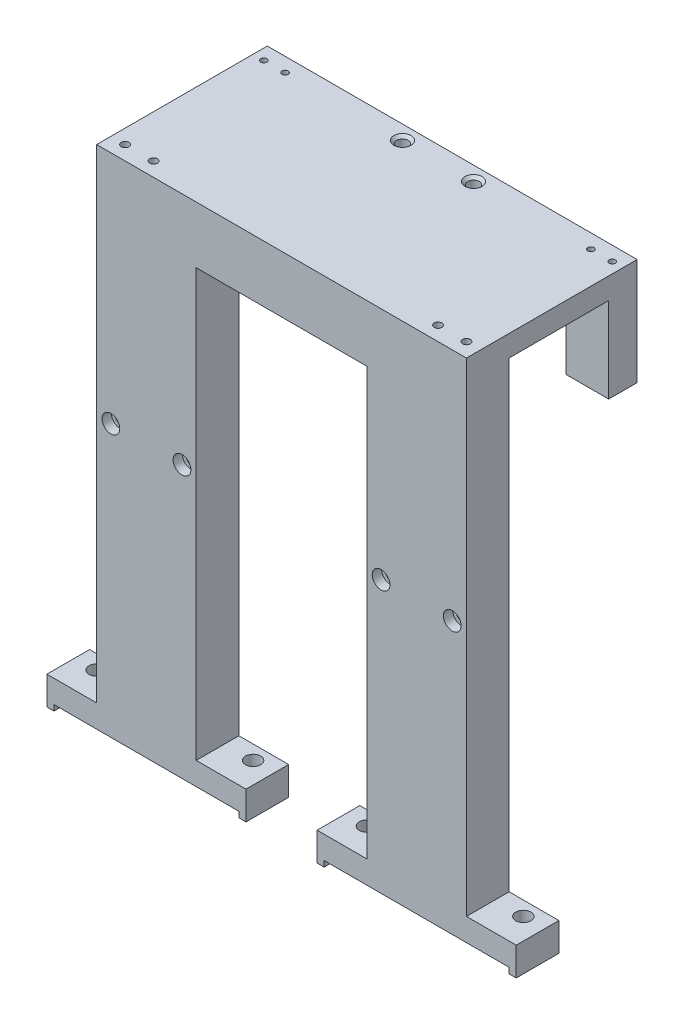
SolidWorks part; units mm, degrees
material "6061 Alloy"
ref_plane "Front Plane" through (0, 0, 0) normal (0, 0, 1) x (1, 0, 0)
ref_plane "Top Plane" through (0, 0, 0) normal (0, 1, 0) x (1, 0, 0)
ref_plane "Right Plane" through (0, 0, 0) normal (1, 0, 0) x (0, 0, -1)
sketch "Sketch1" plane through (0, 0, 0) normal (0, 0, 1) x (1, 0, 0)
  line L1 (-82.55, -114.3) -> (82.55, -114.3)
  line L2 (-82.55, -114.3) -> (-82.55, 114.3)
  line L3 (-82.55, 114.3) -> (82.55, 114.3)
  line L4 (82.55, -114.3) -> (82.55, 114.3)
  line L5 (-82.55, -114.3) -> (82.55, 114.3) construction
  line L6 (-82.55, 114.3) -> (82.55, -114.3) construction
  point P0 (0, 0)
  dimension "D1" = 228.6
  dimension "D2" = 165.1
extrude "Boss-Extrude1" add sketch "Sketch1" along normal blind 19.05
sketch "Sketch2" plane through (0, 0, 19.05) normal (0, 0, 1) x (1, 0, 0)
  line L0 (-82.55, -114.3) -> (82.55, -114.3) construction
  line L1 (-38.1, -114.3) -> (38.1, -114.3)
  line L2 (-38.1, -114.3) -> (-38.1, 88.9)
  line L3 (-38.1, 88.9) -> (38.1, 88.9)
  line L4 (38.1, -114.3) -> (38.1, 88.9)
  line L5 (-82.55, 114.3) -> (-82.55, -114.3) construction
  dimension "D1" = 203.2
  dimension "D2" = 76.2
  dimension "D3" = 44.45
extrude "Cut-Extrude1" cut sketch "Sketch2" against normal through all
sketch "Sketch3" plane through (0, 0, 0) normal (0, 0, -1) x (-1, 0, 0)
  line L0 (82.55, 114.3) -> (82.55, -114.3) construction
  line L1 (-82.55, 114.3) -> (82.55, 114.3)
  line L2 (-82.55, 114.3) -> (-82.55, 104.775)
  line L3 (-82.55, 104.775) -> (82.55, 104.775)
  line L4 (82.55, 114.3) -> (82.55, 104.775)
  dimension "D1" = 9.525
extrude "Boss-Extrude2" add sketch "Sketch3" along normal blind 57.15
sketch "Sketch4" plane through (0, 0, -57.15) normal (0, 0, -1) x (-1, 0, 0)
  line L7 (-82.55, 104.775) -> (-63.5, 104.775)
  line L8 (-82.55, 104.775) -> (-82.55, 66.675)
  line L9 (-82.55, 66.675) -> (-63.5, 66.675)
  line L10 (-63.5, 104.775) -> (-63.5, 66.675)
  dimension "D1" = 38.1
  dimension "D2" = 19.05
extrude "Boss-Extrude3" add sketch "Sketch4" against normal blind 12.7
mirror "Mirror1" about plane through (0, 0, 0) normal (1, 0, 0) of "Boss-Extrude3"
sketch "Sketch7" plane through (0, 0, 19.05) normal (0, 0, 1) x (1, 0, 0)
  line L0 (-82.55, -114.3) -> (-38.1, -114.3) construction
  line L1 (-104.775, -101.6) -> (-15.875, -101.6)
  line L2 (-104.775, -101.6) -> (-104.775, -114.3)
  line L3 (-104.775, -114.3) -> (-15.875, -114.3)
  line L4 (-15.875, -101.6) -> (-15.875, -114.3)
  line L5 (-104.775, -101.6) -> (-15.875, -114.3) construction
  line L6 (-104.775, -114.3) -> (-15.875, -101.6) construction
  line L7 (-82.55, 114.3) -> (-82.55, -114.3) construction
  point P0 (-60.325, -107.95)
  dimension "D1" = 0
  dimension "D2" = 88.9
  dimension "D3" = 22.225
  dimension "D4" = 12.7
extrude "Boss-Extrude4" add sketch "Sketch7" against normal blind 19.05
sketch "Sketch8" plane through (0, -114.3, 0) normal (0, -1, 0) x (-1, 0, 0)
  line L0 (104.775, -19.05) -> (15.875, -19.05) construction
  line L1 (101.6, 0) -> (19.05, 0)
  line L2 (101.6, 0) -> (101.6, -19.05)
  line L3 (101.6, -19.05) -> (19.05, -19.05)
  line L4 (19.05, 0) -> (19.05, -19.05)
  line L5 (101.6, 0) -> (19.05, -19.05) construction
  line L6 (101.6, -19.05) -> (19.05, 0) construction
  line L8 (104.775, 0) -> (104.775, -19.05) construction
  line L9 (15.875, 0) -> (15.875, -19.05) construction
  point P0 (60.325, -9.525)
  dimension "D1" = 19.05
  dimension "D2" = 3.175
  dimension "D3" = 3.175
extrude "Cut-Extrude4" cut sketch "Sketch8" against normal blind 2.54
mirror "Mirror3" about plane through (0, 0, 0) normal (1, 0, 0) of "Cut-Extrude4", "Boss-Extrude4"
hole_wizard "#8-32 Tapped Hole1" positions "Sketch11" profile "Sketch10" tap size "#8-32" standard "ANSI Inch"
sketch "Sketch11" plane through (0, 114.3, 0) normal (0, 1, 0) x (1, 0, 0)
  line L0 (-82.55, 0) -> (-82.55, -19.05) construction
  line L1 (-82.55, -19.05) -> (-82.55, 57.15) construction
  line L2 (82.55, 0) -> (82.55, -19.05) construction
  line L3 (82.55, -19.05) -> (82.55, 57.15) construction
  line L4 (82.55, -19.05) -> (-82.55, -19.05) construction
  point P0 (-76.2, -12.7)
  point P2 (-63.5, -12.7)
  point P4 (63.5, -12.7)
  point P6 (76.2, -12.7)
  dimension "D1" = 6.35
  dimension "D2" = 19.05
  dimension "D3" = 6.35
  dimension "D4" = 19.05
  dimension "D5" = 6.35
  dimension "D6" = 6.35
  dimension "D7" = 6.35
  dimension "D8" = 6.35
cosmetic thread "Hole Thread1" parameters "D1"=3.048, "D2"=4.1656
cosmetic thread "Hole Thread2" parameters "D1"=3.048, "D2"=4.1656
cosmetic thread "Hole Thread3" parameters "D1"=3.048, "D2"=4.1656
cosmetic thread "Hole Thread4" parameters "D1"=3.048, "D2"=4.1656
sketch "Sketch10" plane through (-76.2, 114.3, 12.7) normal (1, 0, 0) x (0, 0, 1)
  line L0 (0, 0) -> (0, 13.7378)
  line L1 (0, 13.7378) -> (1.7272, 12.7)
  line L2 (1.7272, 12.7) -> (1.7272, 0)
  line L5 (1.7272, 0) -> (0, 0)
  line L10 (0, 13.7378) -> (-1.7272, 12.7) construction
  line L11 (0, -6.35) -> (0, 107.95) construction
  dimension "Tap Drill Dia." = 3.4544
  dimension "Tap Drill Depth" = 12.7
  dimension "Drill Angle" = 118
hole_wizard "1/4 Clearance Hole1" positions "Sketch12" profile "Sketch13" hole size "1/4" standard "ANSI Inch" end condition up to next
sketch "Sketch12" plane through (0, -101.6, 0) normal (0, 1, 0) x (1, 0, 0)
  line L0 (-104.775, 0) -> (-104.775, -19.05) construction
  line L1 (-82.55, 0) -> (-104.775, 0) construction
  line L2 (-15.875, 0) -> (-38.1, 0) construction
  line L3 (-15.875, 0) -> (-15.875, -19.05) construction
  line L4 (15.875, 0) -> (15.875, -19.05) construction
  line L5 (15.875, 0) -> (38.1, 0) construction
  line L6 (82.55, 0) -> (104.775, 0) construction
  line L7 (104.775, 0) -> (104.775, -19.05) construction
  point P0 (-95.25, -6.35)
  point P2 (-25.4, -6.35)
  point P4 (25.4, -6.35)
  point P6 (95.25, -6.35)
  dimension "D1" = 9.525
  dimension "D2" = 6.35
  dimension "D3" = 6.35
  dimension "D4" = 9.525
  dimension "D5" = 9.525
  dimension "D6" = 6.35
  dimension "D7" = 6.35
  dimension "D8" = 9.525
sketch "Sketch13" plane through (-95.25, -101.6, 6.35) normal (1, 0, 0) x (0, 0, 1)
  line L0 (0, 0) -> (0, 10.16)
  line L1 (0, 10.16) -> (3.3782, 10.16)
  line L2 (3.3782, 10.16) -> (3.3782, 0)
  line L5 (3.3782, 0) -> (0, 0)
  line L11 (0, -6.35) -> (0, 107.95) construction
  dimension "Thru Hole Dia." = 6.7564
  dimension "Thru Hole Depth" = 10.16
hole_wizard "CBORE for #8 Socket Head Cap Screw1" positions "Sketch18" profile "Sketch19" counterbore size "#8" standard "ANSI Inch" end condition up to next
sketch "Sketch18" plane through (0, 0, 19.05) normal (0, 0, 1) x (1, 0, 0)
  line L0 (-82.55, 114.3) -> (-82.55, -101.6) construction
  line L1 (-38.1, 88.9) -> (-38.1, -101.6) construction
  line L2 (38.1, -101.6) -> (38.1, 88.9) construction
  line L3 (82.55, -101.6) -> (82.55, 114.3) construction
  point P0 (-76.2, 9.525)
  point P2 (-44.45, 9.525)
  point P4 (44.45, 9.525)
  point P6 (76.2, 9.525)
  dimension "D1" = 6.35
  dimension "D2" = 6.35
  dimension "D3" = 6.35
  dimension "D4" = 6.35
  dimension "D5" = 111.125
  dimension "D6" = 111.125
  dimension "D7" = 111.125
  dimension "D8" = 111.125
sketch "Sketch19" plane through (-76.2, 9.525, 19.05) normal (1, 0, 0) x (0, -1, 0)
  line L0 (0, 0) -> (0, 19.05)
  line L1 (0, 19.05) -> (2.2479, 19.05)
  line L3 (2.2479, 19.05) -> (2.2479, 4.1656)
  line L4 (2.2479, 4.1656) -> (3.9687, 4.1656)
  line L5 (3.9687, 4.1656) -> (3.9687, 0)
  line L7 (3.9687, 0) -> (0, 0)
  line L11 (0, -6.35) -> (0, 107.95) construction
  dimension "Thru Hole Dia." = 4.4958
  dimension "Thru Hole Depth" = 19.05
  dimension "C'Bore Dia." = 7.9375
  dimension "C'Bore Depth" = 4.1656
hole_wizard "1/4-20 Tapped Hole1" positions "Sketch20" profile "Sketch21" tap size "1/4-20" standard "ANSI Inch" end condition through all
sketch "Sketch20" plane through (0, 114.3, 0) normal (0, 1, 0) x (1, 0, 0)
  line L0 (-82.55, -19.05) -> (-82.55, 57.15) construction
  line L1 (82.55, -19.05) -> (82.55, 57.15) construction
  line L2 (-82.55, 57.15) -> (82.55, 57.15) construction
  point P0 (15.875, 50.8)
  point P2 (-15.875, 50.8)
  dimension "D1" = 66.675
  dimension "D2" = 66.675
  dimension "D3" = 6.35
  dimension "D4" = 6.35
sketch "Sketch21" plane through (15.875, 114.3, -50.8) normal (1, 0, 0) x (0, 0, 1)
  line L0 (0, 0) -> (0, 228.6)
  line L1 (0, 228.6) -> (2.5527, 228.6)
  line L2 (2.5527, 228.6) -> (2.5527, 1.2573)
  line L3 (2.5527, 1.2573) -> (3.81, 0)
  line L5 (3.81, 0) -> (0, 0)
  line L6 (-2.5527, 1.2573) -> (-3.81, 0) construction
  line L11 (0, -6.35) -> (0, 107.95) construction
  dimension "Thru Tap Drill Dia." = 5.1054
  dimension "Thru Tap Drill Depth" = 228.6
  dimension "Near C'Sink Dia." = 7.62
  dimension "Near C'Sink Angle" = 90
cosmetic thread "Hole Thread5" parameters "D2"=6.35
cosmetic thread "Hole Thread6" parameters "D2"=6.35
sketch "Sketch22" plane through (0, 0, -57.15) normal (0, 0, -1) x (-1, 0, 0)
  line L0 (-63.5, 104.775) -> (63.5, 104.775) construction
  line L1 (3.175, 98.425) -> (-3.175, 98.425)
  line L2 (3.175, 98.425) -> (3.175, 104.775)
  line L3 (3.175, 104.775) -> (-3.175, 104.775)
  line L4 (-3.175, 98.425) -> (-3.175, 104.775)
  line L5 (3.175, 98.425) -> (-3.175, 104.775) construction
  line L6 (3.175, 104.775) -> (-3.175, 98.425) construction
  point P0 (0, 101.6)
  dimension "D1" = 6.35
  dimension "D2" = 6.35
  dimension "D3" = 0
extrude "Boss-Extrude5" add sketch "Sketch22" along normal blind 3.175 from offset 7.9375 separate body offset against normal yes
sketch "Sketch23" plane through (0, 0, -52.3875) normal (0, 0, -1) x (-1, 0, 0)
  line L0 (-3.175, 98.425) -> (3.175, 98.425) construction
  line L1 (-3.175, 104.775) -> (-3.175, 98.425) construction
  circle A0 centre (0, 101.6) radius 1.5875
  dimension "D3" = 3.175
  dimension "D1" = 3.175
  dimension "D2" = 3.175
extrude "Cut-Extrude5" cut sketch "Sketch23" against normal up to next (3.175 mm away)
hole_wizard "#6-32 Tapped Hole1" positions "Sketch24" profile "Sketch25" tap size "#6-32" standard "ANSI Inch" end condition up to next
sketch "Sketch24" plane through (0, 66.675, 0) normal (0, -1, 0) x (-1, 0, 0)
  line L0 (82.55, 44.45) -> (82.55, 57.15) construction
  line L1 (-82.55, 44.45) -> (-82.55, 57.15) construction
  line L2 (82.55, 44.45) -> (63.5, 44.45) construction
  line L3 (63.5, 44.45) -> (82.55, 44.45) construction
  line L4 (-82.55, 44.45) -> (-63.5, 44.45) construction
  line L5 (-63.5, 44.45) -> (-82.55, 44.45) construction
  point P0 (-77.7875, 50.8)
  point P2 (-68.2625, 50.8)
  point P4 (68.2625, 50.8)
  point P6 (77.7875, 50.8)
  dimension "D1" = 4.7625
  dimension "D2" = 4.7625
  dimension "D3" = 9.525
  dimension "D4" = 9.525
  dimension "D5" = 6.35
  dimension "D6" = 6.35
  dimension "D7" = 6.35
  dimension "D8" = 6.35
sketch "Sketch25" plane through (77.7875, 66.675, -50.8) normal (1, 0, 0) x (0, 0, -1)
  line L0 (0, 0) -> (0, 47.625)
  line L1 (0, 47.625) -> (1.3525, 47.625)
  line L2 (1.3525, 47.625) -> (1.3525, 0)
  line L5 (1.3525, 0) -> (0, 0)
  line L11 (0, -6.35) -> (0, 107.95) construction
  dimension "Thru Tap Drill Dia." = 2.7051
  dimension "Thru Tap Drill Depth" = 47.625
cosmetic thread "Hole Thread7" parameters "D2"=3.5052
cosmetic thread "Hole Thread8" parameters "D2"=3.5052
cosmetic thread "Hole Thread9" parameters "D2"=3.5052
cosmetic thread "Hole Thread10" parameters "D2"=3.5052
